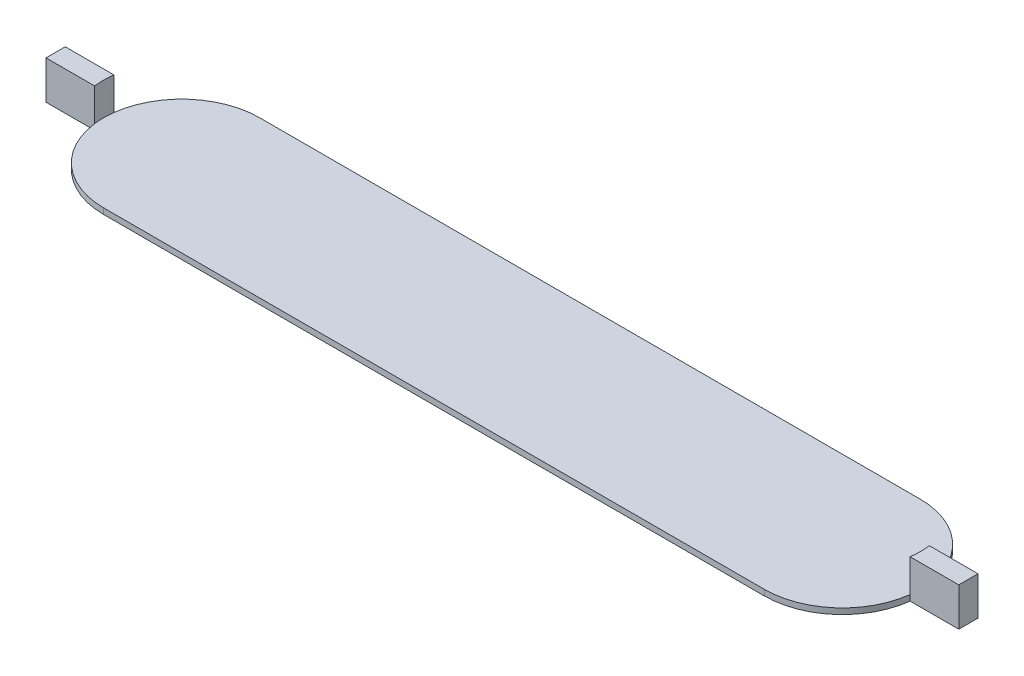
SolidWorks part; units mm, degrees
ref_plane "Front Plane" through (0, 0, 0) normal (0, 0, 1) x (1, 0, 0)
ref_plane "Top Plane" through (0, 0, 0) normal (0, 1, 0) x (1, 0, 0)
ref_plane "Right Plane" through (0, 0, 0) normal (1, 0, 0) x (0, 0, -1)
sketch "Sketch2" plane through (0, 0, 0) normal (0, 1, 0) x (1, 0, 0)
  line L0 (-290.128, -41.6591) -> (397.4644, -41.6591) construction
  line L1 (-290.128, 39.5447) -> (397.4644, 39.5447)
  line L2 (-290.128, -122.8629) -> (397.4644, -122.8629)
  line L3 (-371.3318, -41.6591) -> (-290.128, -41.6591) construction
  line L4 (-421.3318, -31.6591) -> (-370.7137, -31.6591)
  line L5 (-421.3318, -31.6591) -> (-421.3318, -51.6591)
  line L6 (-421.3318, -51.6591) -> (-370.7137, -51.6591)
  line L7 (528.6682, -31.6591) -> (478.0501, -31.6591)
  line L8 (528.6682, -51.6591) -> (478.0501, -51.6591)
  line L9 (528.6682, -51.6591) -> (528.6682, -31.6591)
  arc A0 (-290.128, 39.5447) -> (-290.128, -122.8629) centre (-290.128, -41.6591) ccw
  arc A1 (397.4644, -122.8629) -> (397.4644, 39.5447) centre (397.4644, -41.6591) ccw
  point P2 (53.6682, -41.6591)
extrude "Boss-Extrude1" add sketch "Sketch2" along normal blind 6 contours L2 A1 L1 A0 region at (53.6682, 0, 41.6591)
extrude "Boss-Extrude2" add sketch "Sketch2<3>" along normal blind 40 contours A0 L4 L5 L6 | A1 L8 L9 L7 region at (-396.2286, 0, 41.6591) region at (503.565, 0, 41.6591)
sketch "Sketch2<3>" plane through (0, 0, 0) normal (0, 1, 0) x (1, 0, 0) same geometry as "Sketch2"
